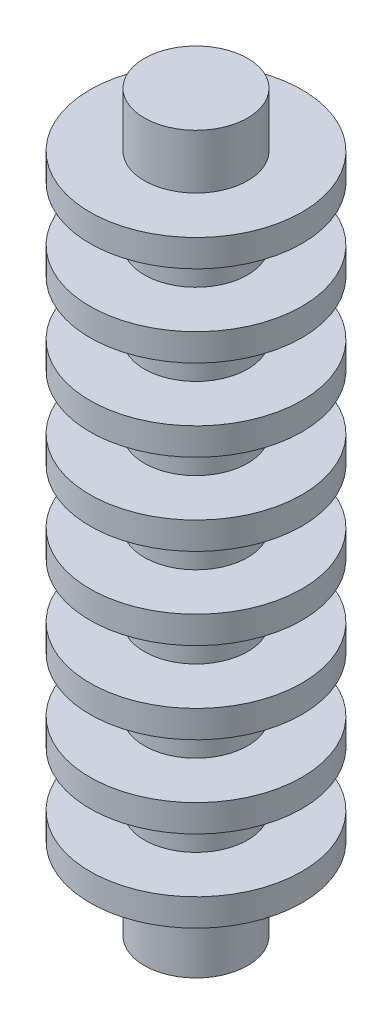
SolidWorks part; units mm, degrees
ref_plane "Front Plane" through (0, 0, 0) normal (0, 0, 1) x (1, 0, 0)
ref_plane "Top Plane" through (0, 0, 0) normal (0, 1, 0) x (1, 0, 0)
ref_plane "Right Plane" through (0, 0, 0) normal (1, 0, 0) x (0, 0, -1)
sketch "Sketch1" plane through (0, 0, 0) normal (0, 0, 1) x (1, 0, 0)
  line L0 (0, -24) -> (0, 24) construction
  line L1 (3.8, 24) -> (3.8, 23)
  line L2 (-19.9325, 24) -> (3.8, 24) construction
  line L3 (3.8, 18) -> (3.8, 17)
  line L4 (3.8, 17) -> (7.8, 17)
  line L5 (3.8, 23) -> (7.8, 23)
  line L6 (7.8, 23) -> (7.8, 21)
  line L7 (7.8, 21) -> (3.8, 21)
  line L8 (3.8, 21) -> (3.8, 18)
  line L9 (3.8, 24) -> (3.8, 27)
  line L10 (3.8, 27) -> (0, 27)
  line L11 (3.8, -24) -> (3.8, -27)
  line L12 (3.8, -27) -> (0, -27)
  line L13 (7.8, 17) -> (7.8, 15)
  line L14 (7.8, 15) -> (3.8, 15)
  line L15 (3.8, 15) -> (3.8, 12)
  line L16 (0, 27) -> (0, -27)
  line L20 (3.8, 12) -> (3.8, 11)
  line L21 (3.8, 11) -> (7.8, 11)
  line L22 (7.8, 11) -> (7.8, 9)
  line L23 (7.8, 9) -> (3.8, 9)
  line L24 (3.8, 9) -> (3.8, 6)
  line L29 (3.8, 6) -> (3.8, 5)
  line L30 (3.8, 5) -> (7.8, 5)
  line L31 (7.8, 5) -> (7.8, 3)
  line L32 (7.8, 3) -> (3.8, 3)
  line L33 (3.8, 3) -> (3.8, 0)
  line L38 (3.8, 0) -> (3.8, -1)
  line L39 (3.8, -1) -> (7.8, -1)
  line L40 (7.8, -1) -> (7.8, -3)
  line L41 (7.8, -3) -> (3.8, -3)
  line L42 (3.8, -3) -> (3.8, -6)
  line L47 (3.8, -6) -> (3.8, -7)
  line L48 (3.8, -7) -> (7.8, -7)
  line L49 (7.8, -7) -> (7.8, -9)
  line L50 (7.8, -9) -> (3.8, -9)
  line L51 (3.8, -9) -> (3.8, -12)
  line L56 (3.8, -12) -> (3.8, -13)
  line L57 (3.8, -13) -> (7.8, -13)
  line L58 (7.8, -13) -> (7.8, -15)
  line L59 (7.8, -15) -> (3.8, -15)
  line L60 (3.8, -15) -> (3.8, -18)
  line L65 (3.8, -18) -> (3.8, -19)
  line L66 (3.8, -19) -> (7.8, -19)
  line L67 (7.8, -19) -> (7.8, -21)
  line L68 (7.8, -21) -> (3.8, -21)
  line L69 (3.8, -21) -> (3.8, -24)
  point P3 (0, 0)
  point P4 (0, 0)
  dimension "D1" = 48
  dimension "D2" = 3.8
  dimension "D3" = 3
  dimension "D4" = 3
  dimension "D7" = 2
  dimension "D11" = 4
  dimension "D12" = 8
revolve "Revolve1" add sketch "Sketch1" angle 360 about L16
